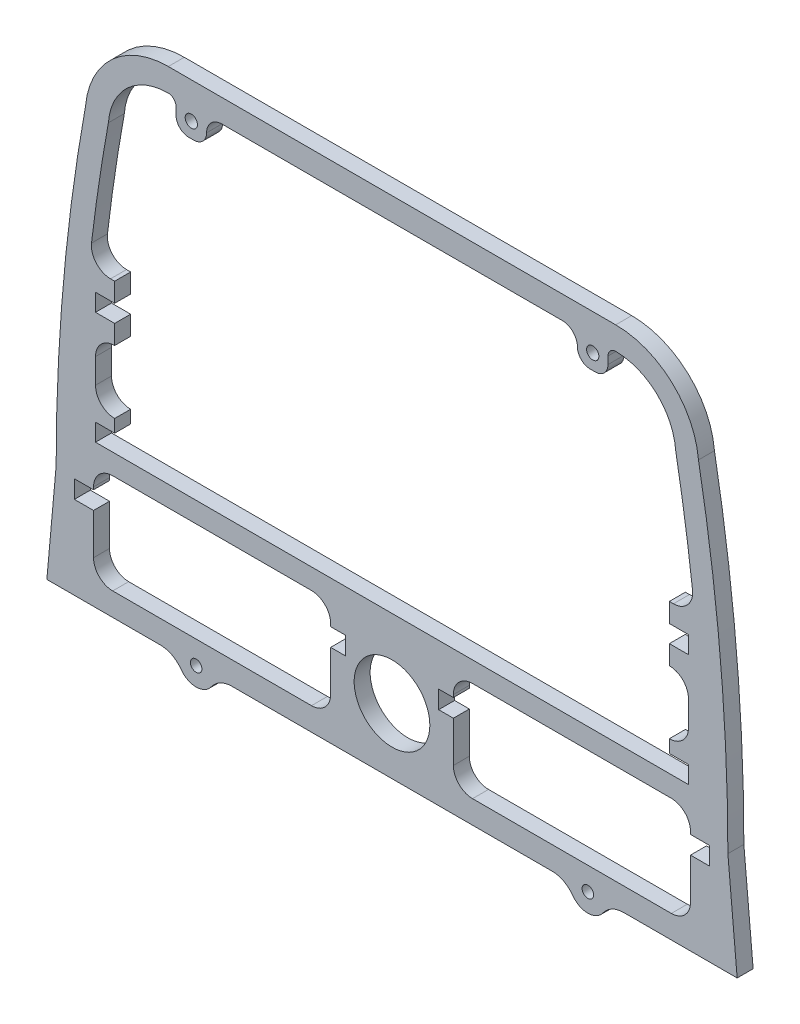
SolidWorks part; units mm, degrees
material "Delrin 2700 NC010, Low Viscosity Acetal Copolymer (SS)"
ref_plane "Front Plane" through (0, 0, 0) normal (0, 0, 1) x (1, 0, 0)
ref_plane "Top Plane" through (0, 0, 0) normal (0, 1, 0) x (1, 0, 0)
ref_plane "Right Plane" through (0, 0, 0) normal (1, 0, 0) x (0, 0, -1)
sketch "Sketch1" plane through (0, 0, 0) normal (0, 0, 1) x (1, 0, 0)
  line L0 (33.3676, -11.9888) -> (34.29, -22.225)
  line L1 (22.225, 27.94) -> (-22.225, 27.94)
  line L2 (-34.29, -22.225) -> (-30.4467, 20.4259) construction
  line L3 (-33.3676, -11.9888) -> (-33.3676, 14.6458) construction
  line L4 (-33.3676, -11.9888) -> (-34.29, -22.225)
  line L5 (16.9079, 25.654) -> (-16.9079, 25.654)
  line L6 (6.096, -13.97) -> (6.096, -19.939)
  line L7 (-29.6529, -19.939) -> (-6.096, -19.939)
  line L8 (-34.29, -22.225) -> (-21.299, -22.225)
  line L9 (-29.6529, -10.033) -> (-29.6529, -12.192)
  line L10 (18.4213, 24.1407) -> (18.4213, 24.1363)
  line L11 (19.6913, 22.8663) -> (20.1867, 22.8663)
  line L12 (21.4567, 24.1363) -> (21.4567, 24.8713)
  line L13 (-21.4567, 24.1363) -> (-21.4567, 24.8713)
  line L14 (-19.6913, 22.8663) -> (-20.1867, 22.8663)
  line L15 (-18.4213, 24.1407) -> (-18.4213, 24.1363)
  line L16 (29.4572, -8.001) -> (-29.4572, -8.001)
  line L17 (29.6529, -10.033) -> (6.096, -10.033)
  line L18 (0, 18.415) -> (0, -18.415) construction
  line L19 (-1007.9925, 0) -> (48992.0075, 0) construction
  line L20 (-6.096, -10.033) -> (-29.6529, -10.033)
  line L21 (19.939, 24.384) -> (21.4567, 24.384) construction
  line L22 (6.096, -19.939) -> (29.6529, -19.939)
  line L23 (-6.096, -10.033) -> (-6.096, -12.192)
  line L24 (5.9491, -2.2098) -> (59.5431, -2.2098) construction
  line L25 (5.9491, -2.2098) -> (5.9491, -11.9888) construction
  line L26 (3.4091, -11.9888) -> (-3.4091, -11.9888) construction
  line L27 (59.5431, -2.2098) -> (59.5431, -11.9888) construction
  line L28 (-31.7887, -19.939) -> (31.7887, -19.939) construction
  line L29 (22.225, 25.654) -> (-22.225, 25.654) construction
  line L30 (-6.096, -19.939) -> (-6.1666, -19.9899)
  line L31 (29.4572, -6.2738) -> (27.5522, -6.2738)
  line L32 (27.5522, -6.2738) -> (27.5522, -5.0038)
  line L33 (-29.6529, -12.192) -> (-31.5579, -12.192)
  line L34 (27.5522, -5.0038) -> (29.4572, -5.0038)
  line L35 (29.4572, 1.27) -> (27.5522, 1.27)
  line L36 (27.5522, 1.27) -> (27.5522, 3.175)
  line L37 (27.5522, 3.175) -> (29.4572, 3.175)
  line L38 (29.4572, 4.9022) -> (27.5522, 4.9022)
  line L39 (19.939, 24.384) -> (18.4213, 24.384) construction
  line L40 (27.5522, 4.9022) -> (27.5522, 6.8072)
  line L41 (27.5522, 6.8072) -> (30.0922, 6.8072)
  line L42 (19.939, 24.384) -> (19.939, 22.8663) construction
  line L43 (6.096, -10.033) -> (6.096, -12.192)
  line L44 (-29.4572, -6.2738) -> (-29.4572, -8.001)
  line L45 (-29.4572, -6.2738) -> (-27.5522, -6.2738)
  line L46 (-27.5522, -6.2738) -> (-27.5522, -5.0038)
  line L47 (-27.5522, -5.0038) -> (-29.4572, -5.0038)
  line L48 (-29.4572, 1.27) -> (-29.4572, -5.0038)
  line L49 (-29.4572, 1.27) -> (-27.5522, 1.27)
  line L50 (-27.5522, 1.27) -> (-27.5522, 3.175)
  line L51 (-27.5522, 3.175) -> (-29.4572, 3.175)
  line L52 (-29.4572, 4.9022) -> (-29.4572, 3.175)
  line L53 (-31.5579, -12.192) -> (-31.5579, -13.97)
  line L54 (-31.5579, -13.97) -> (-29.6529, -13.97)
  line L55 (-6.096, -12.192) -> (-4.6339, -12.192)
  line L56 (-4.6339, -12.192) -> (-4.6339, -13.97)
  line L57 (-4.6339, -13.97) -> (-6.096, -13.97)
  line L58 (-29.6529, -10.033) -> (-29.6529, -19.939) construction
  line L59 (-29.6529, -14.986) -> (-33.4249, -14.986) construction
  line L60 (-29.6529, -14.986) -> (-0.4824, -14.986) construction
  line L61 (-6.096, -13.97) -> (-6.096, -19.939)
  line L62 (-29.6529, -19.939) -> (-29.6529, -13.97)
  line L63 (29.6529, -19.939) -> (29.6529, -13.97)
  line L64 (-31.0816, -12.0913) -> (-31.7887, -19.939) construction
  line L65 (29.6529, -10.033) -> (29.6529, -12.192)
  line L66 (31.5579, -13.97) -> (29.6529, -13.97)
  line L67 (31.5579, -12.192) -> (31.5579, -13.97)
  line L68 (29.6529, -12.192) -> (31.5579, -12.192)
  line L69 (6.096, -12.192) -> (4.6339, -12.192)
  line L70 (4.6339, -12.192) -> (4.6339, -13.97)
  line L71 (4.6339, -13.97) -> (6.096, -13.97)
  line L72 (29.4572, 4.9022) -> (29.4572, 3.175)
  line L73 (31.0816, -12.0913) -> (31.7887, -19.939) construction
  line L74 (29.4572, 1.27) -> (29.4572, -5.0038)
  line L75 (29.4572, -6.2738) -> (29.4572, -8.001)
  line L76 (-29.4572, 4.9022) -> (-27.5522, 4.9022)
  line L77 (-27.5522, 4.9022) -> (-27.5522, 6.8072)
  line L78 (-27.5522, 6.8072) -> (-30.0922, 6.8072)
  line L79 (-17.616, -22.225) -> (17.616, -22.225)
  line L80 (21.299, -22.225) -> (34.29, -22.225)
  line L81 (-34.29, -22.225) -> (34.29, -22.225) construction
  arc A0 (22.225, 27.94) -> (30.4467, 20.4259) centre (22.225, 19.685) cw
  arc A1 (-22.225, 27.94) -> (-30.4467, 20.4259) centre (-22.225, 19.685) ccw
  arc A2 (33.3676, -11.9888) -> (30.4467, 20.4259) centre (-147.9525, -11.9888) ccw
  circle A3 centre (0, -15.748) radius 3.7592
  circle A4 centre (19.4575, -22.225) radius 0.5715
  arc A5 (-33.3676, -11.9888) -> (-30.4467, 20.4259) centre (147.9525, -11.9888) cw
  arc A6 (-17.616, -22.225) -> (-21.299, -22.225) centre (-19.4575, -22.225) cw
  arc A7 (17.616, -22.225) -> (21.299, -22.225) centre (19.4575, -22.225) ccw
  arc A8 (20.1867, 22.8663) -> (21.4567, 24.1363) centre (20.1867, 24.1363) ccw
  circle A9 centre (-19.939, 24.384) radius 0.6096
  circle A10 centre (19.939, 24.384) radius 0.6096
  arc A11 (18.4213, 24.1363) -> (19.6913, 22.8663) centre (19.6913, 24.1363) ccw
  circle A12 centre (-19.4575, -22.225) radius 0.5715
  arc A13 (18.4213, 24.1407) -> (16.9079, 25.654) centre (16.9079, 24.1407) ccw
  arc A14 (22.2416, 25.654) -> (21.4567, 24.8713) centre (22.2394, 24.8713) ccw
  arc A15 (-22.2416, 25.654) -> (-21.4567, 24.8713) centre (-22.2394, 24.8713) cw
  arc A16 (-20.1867, 22.8663) -> (-21.4567, 24.1363) centre (-20.1867, 24.1363) cw
  arc A17 (-18.4213, 24.1363) -> (-19.6913, 22.8663) centre (-19.6913, 24.1363) cw
  arc A18 (-22.2416, 25.654) -> (-28.1777, 20.1262) centre (-22.225, 19.685) ccw
  arc A19 (-18.4213, 24.1407) -> (-16.9079, 25.654) centre (-16.9079, 24.1407) cw
  arc A20 (31.0816, -12.0913) -> (31.0816, -11.9888) centre (-147.9525, -11.9888) ccw
  circle A21 centre (-19.4575, -22.225) radius 1.8415 construction
  arc A23 (22.2416, 25.654) -> (28.1777, 20.1262) centre (22.225, 19.685) cw
  arc A25 (-22.225, 25.654) -> (-28.1777, 20.1262) centre (-22.225, 19.685) ccw construction
  arc A26 (22.225, 25.654) -> (28.1777, 20.1262) centre (22.225, 19.685) cw construction
  arc A28 (-31.0816, -12.0913) -> (-28.1777, 20.1262) centre (147.9525, -11.9888) cw construction
  arc A30 (31.0816, -12.0913) -> (28.1777, 20.1262) centre (-147.9525, -11.9888) ccw construction
  arc A31 (30.0922, 6.8072) -> (28.1777, 20.1262) centre (-147.9525, -11.9888) ccw
  arc A33 (-30.0922, 6.8072) -> (-28.1777, 20.1262) centre (147.9525, -11.9888) cw
  point P0 (0, 0)
  point P1 (0, 27.94)
  point P31 (0, -11.9888)
  point P121 (-30.9018, -14.986)
  point P135 (-17.616, -22.225)
  dimension "D4" = 2.286
  dimension "D6" = 8.255
  dimension "D7" = 19.4575
  dimension "D8" = 50.165
  dimension "D9" = 15.748
  dimension "D5" = 1.2192
  dimension "D17" = 1.143
  dimension "D3" = 7.5184
  dimension "D18" = 1.27
  dimension "D19" = 1.27
  dimension "D26" = 11.176
  dimension "D28" = 0.7827
  dimension "D29" = 1.5133
  dimension "D32" = 1.905
  dimension "D2" = 44.45
  dimension "D10" = 1.27
  dimension "D11" = 1.27
  dimension "D12" = 68.58
  dimension "D13" = 19.939
  dimension "D14" = 22.225
  dimension "D15" = 53.594
  dimension "D16" = 9.779
  dimension "D20" = 6.096
  dimension "D21" = 11.938
  dimension "D22" = 2.032
  dimension "D23" = 1.7272
  dimension "D24" = 1.27
  dimension "D25" = 1.905
  dimension "D27" = 0.4954
  dimension "D30" = 1.905
  dimension "D31" = 1.7272
  dimension "D33" = 1.778
  dimension "D34" = 2.159
  dimension "D35" = 23.5569
  dimension "D36" = 26.924
  dimension "D37" = 1.905
  dimension "D38" = 2.54
extrude "Boss-Extrude1" add sketch "Sketch1" along normal blind 1.5875 contours L8 A12 A4 L0 A2 A0 L1 A1 A5 L4 L74 L16 A18 A15 L13 A16 L14 A17 L15 A19 L5 A13 L10 A11 L11 A8 L12 A14 A23 A20 L22 L43 L17 A10 A9 A3 L20 region at (32.9716, -17.1841, 0)
ref_axis "Axis1" through (0, -15.748, 0) along (0, 0, 1)
fillet "Fillet1" radius 1.905 8 edges at (-6.096, -10.033, 0.7937) (6.096, -10.033, 0.7937) (-6.096, -19.939, 0.7937) (-29.6529, -19.939, 0.7937) (-29.6529, -10.033, 0.7937) (6.096, -19.939, 0.7937) (29.6529, -19.939, 0.7937) (29.6529, -10.033, 0.7937)
fillet "Fillet2" radius 1.905 6 edges at (-29.4572, 1.27, 0.7937) (-29.4572, -5.0038, 0.7937) (-30.0922, 6.8072, 0.7937) (29.4572, -5.0038, 0.7937) (29.4572, 1.27, 0.7937) (30.0922, 6.8072, 0.7937)
fillet "Fillet3" radius 2.54 4 edges at (-17.616, -22.225, 0.7937) (-21.299, -22.225, 0.7937) (17.616, -22.225, 0.7937) (21.299, -22.225, 0.7937)
